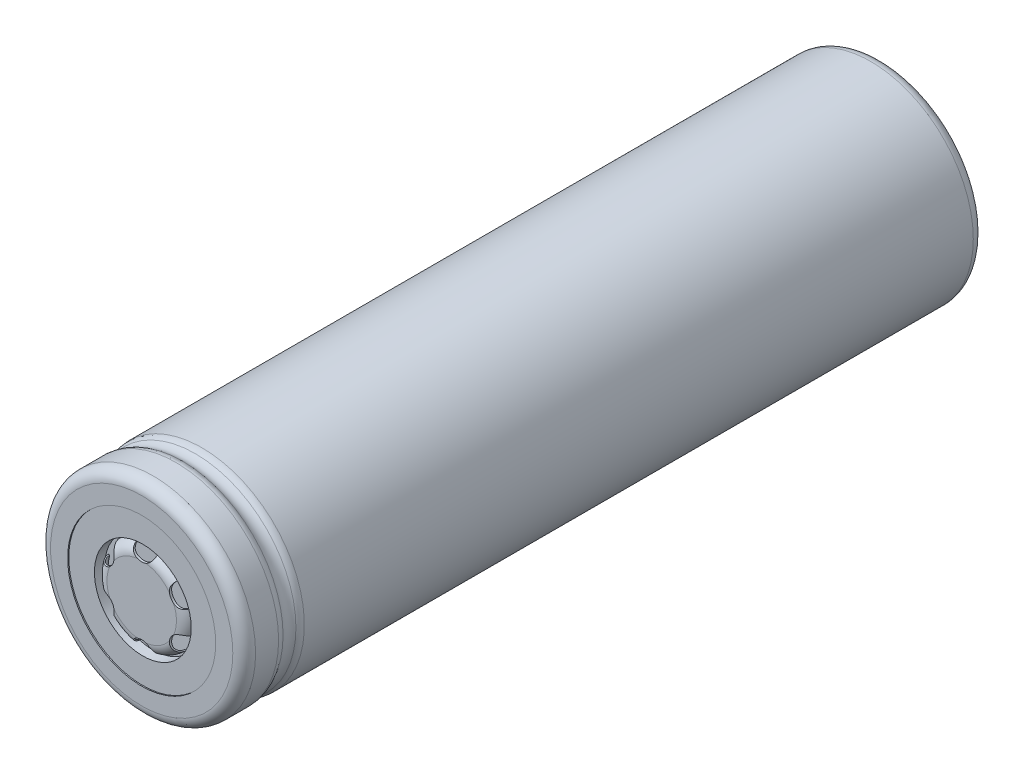
SolidWorks part; units mm, degrees
ref_plane "Спереди" through (0, 0, 0) normal (0, 0, 1) x (1, 0, 0)
ref_plane "Сверху" through (0, 0, 0) normal (0, 1, 0) x (1, 0, 0)
ref_plane "Справа" through (0, 0, 0) normal (1, 0, 0) x (0, 0, -1)
sketch "Эскиз1" plane through (0, 0, 0) normal (0, 0, 1) x (1, 0, 0)
  circle A0 centre (0, 0) radius 9
  dimension "D1" = 18
extrude "Бобышка-Вытянуть1" add sketch "Эскиз1" along normal blind 65
sketch "Эскиз2" plane through (0, 0, 65) normal (0, 0, 1) x (1, 0, 0)
  circle A0 centre (0, 0) radius 4.25
  circle A1 centre (0, 0) radius 4.05
  dimension "D1" = 8.5
  dimension "D2" = 8.1
extrude "Вырез-Вытянуть1" cut sketch "Эскиз2" against normal blind 1
sketch "Эскиз3" plane through (0, 0, 65) normal (0, 0, 1) x (1, 0, 0)
  circle A0 centre (0, 0) radius 6.5
  circle A1 centre (0, 0) radius 4.25 construction
  circle A2 centre (0, 0) radius 4.25
  dimension "D1" = 13
extrude "Вырез-Вытянуть2" cut sketch "Эскиз3" against normal blind 0.1
fillet "Скругление1" radius 1 2 edges at (9, 0, 0) (9, 0, 65)
sketch "Эскиз4" plane through (0, 0, 0) normal (0, 0, -1) x (-1, 0, 0)
  circle A0 centre (0, 0) radius 6.5
  dimension "D1" = 13
extrude "Вырез-Вытянуть3" cut sketch "Эскиз4" against normal blind 0.1
fillet "Скругление2" radius 1 1 edges at (4.05, 0, 65)
sketch "Эскиз5" plane through (0, 0, 65) normal (0, 0, 1) x (1, 0, 0)
  line L0 (0, 0) -> (0, 4.25) construction
  circle A0 centre (0, 0) radius 4.25 construction
  arc A1 (-0.9994, 3.9248) -> (0.9994, 3.9248) centre (0, 3.9601) ccw
  circle A2 centre (0, 0) radius 4.05 construction
  arc A4 (2.8993, 2.8279) -> (3.8986, 1.0969) centre (3.4296, 1.9801) ccw
  arc A5 (3.8986, -1.0969) -> (2.8993, -2.8279) centre (3.4296, -1.9801) ccw
  arc A6 (0.9994, -3.9248) -> (-0.9994, -3.9248) centre (0, -3.9601) ccw
  arc A7 (-2.8993, -2.8279) -> (-3.8986, -1.0969) centre (-3.4296, -1.9801) ccw
  arc A8 (-3.8986, 1.0969) -> (-2.8993, 2.8279) centre (-3.4296, 1.9801) ccw
  arc A9 (-2.8993, 2.8279) -> (-3.8986, 1.0969) centre (0, 0) ccw
  arc A10 (0.9994, 3.9248) -> (-0.9994, 3.9248) centre (0, 0) ccw
  arc A11 (3.8986, 1.0969) -> (2.8993, 2.8279) centre (0, 0) ccw
  arc A12 (2.8993, -2.8279) -> (3.8986, -1.0969) centre (0, 0) ccw
  arc A13 (-0.9994, -3.9248) -> (0.9994, -3.9248) centre (0, 0) ccw
  arc A14 (-3.8986, -1.0969) -> (-2.8993, -2.8279) centre (0, 0) ccw
  point P28 (0, 0)
  dimension "D1" = 1
  dimension "D2" = 1.9987
  dimension "D3" = 6
extrude "Вырез-Вытянуть4" cut sketch "Эскиз5" against normal blind 1
sketch "Эскиз6" plane through (0, 0, 0) normal (0, 1, 0) x (1, 0, 0)
  line L2 (0.3629, -65) -> (2.4411, -65) construction
  line L3 (-2.4411, -65) -> (-0.3629, -65) construction
  line L4 (0.3629, -65) -> (2.4411, -65)
  line L5 (-2.4411, -65) -> (-0.3629, -65)
  line L8 (-3.2, -64.8) -> (0, -64.8)
  line L9 (-2.4411, -64.8) -> (-0.3629, -64.8) construction
  line L10 (0, 0) -> (0, -67.0085) construction
  line L11 (-3.95, -64.05) -> (0, -64.05)
  line L12 (0, -64.05) -> (0, -64.8)
  arc A0 (-3.2, -64.8) -> (-3.95, -64.05) centre (-3.2, -64.05) cw
  point P11 (0, 0)
  dimension "D3" = 3.2
  dimension "D2" = 0.75
  dimension "D1" = 0.2
revolve "Вырез-Повернуть1" cut sketch "Эскиз6" angle 360 about L10 region at (-1.8982, 0, 64.4162)
sketch "Эскиз7" plane through (0, 0, 64.05) normal (0, 0, 1) x (1, 0, 0)
  arc A12 (2.8161, 2.7698) -> (3.8068, 1.0539) centre (3.4296, 1.9801) ccw
  arc A13 (2.8161, 2.7698) -> (0.9907, 3.8238) centre (0, 0) ccw
  arc A14 (-0.9907, 3.8238) -> (0.9907, 3.8238) centre (0, 3.9601) ccw
  arc A15 (-0.9907, 3.8238) -> (-2.8161, 2.7698) centre (0, 0) ccw
  arc A16 (-3.8068, 1.0539) -> (-2.8161, 2.7698) centre (-3.4296, 1.9801) ccw
  arc A17 (-3.8068, 1.0539) -> (-3.8068, -1.0539) centre (0, 0) ccw
  arc A18 (-2.8161, -2.7698) -> (-3.8068, -1.0539) centre (-3.4296, -1.9801) ccw
  arc A19 (-2.8161, -2.7698) -> (-0.9907, -3.8238) centre (0, 0) ccw
  arc A20 (0.9907, -3.8238) -> (-0.9907, -3.8238) centre (0, -3.9601) ccw
  arc A21 (0.9907, -3.8238) -> (2.8161, -2.7698) centre (0, 0) ccw
  arc A22 (3.8068, -1.0539) -> (2.8161, -2.7698) centre (3.4296, -1.9801) ccw
  arc A23 (3.8068, -1.0539) -> (3.8068, 1.0539) centre (0, 0) ccw
  arc A24 (2.8161, 2.7698) -> (3.8068, 1.0539) centre (3.4296, 1.9801) ccw
  arc A25 (2.8161, 2.7698) -> (0.9907, 3.8238) centre (0, 0) ccw
  arc A26 (-0.9907, 3.8238) -> (0.9907, 3.8238) centre (0, 3.9601) ccw
  arc A27 (-0.9907, 3.8238) -> (-2.8161, 2.7698) centre (0, 0) ccw
  arc A28 (-3.8068, 1.0539) -> (-2.8161, 2.7698) centre (-3.4296, 1.9801) ccw
  arc A29 (-3.8068, 1.0539) -> (-3.8068, -1.0539) centre (0, 0) ccw
  arc A30 (-2.8161, -2.7698) -> (-3.8068, -1.0539) centre (-3.4296, -1.9801) ccw
  arc A31 (-2.8161, -2.7698) -> (-0.9907, -3.8238) centre (0, 0) ccw
  arc A32 (0.9907, -3.8238) -> (-0.9907, -3.8238) centre (0, -3.9601) ccw
  arc A33 (0.9907, -3.8238) -> (2.8161, -2.7698) centre (0, 0) ccw
  arc A34 (3.8068, -1.0539) -> (2.8161, -2.7698) centre (3.4296, -1.9801) ccw
  arc A35 (3.8068, -1.0539) -> (3.8068, 1.0539) centre (0, 0) ccw
  dimension "D1" = 0
extrude "Вырез-Вытянуть5" cut sketch "Эскиз7" against normal up to surface (0.05 mm away) up to face at (0, 0, 64)
sketch "Эскиз8" plane through (0, 0, 0) normal (0, 1, 0) x (1, 0, 0)
  line L0 (9.5867, -61.848) -> (9.5867, -59.852)
  line L1 (-8, -65) -> (8, -65) construction
  line L2 (0, 0) -> (0, -84.4174) construction
  arc A0 (9.5867, -61.848) -> (9.5867, -59.852) centre (9.65, -60.85) cw
  dimension "D2" = 1
  dimension "D1" = 4.15
  dimension "D3" = 9.65
  dimension "D4" = 1.996
revolve "Вырез-Повернуть2" cut sketch "Эскиз8" angle 360 about L2
fillet "Скругление3" radius 1 2 edges at (-9, 0, 61.6099) (9, 0, 60.0901)
